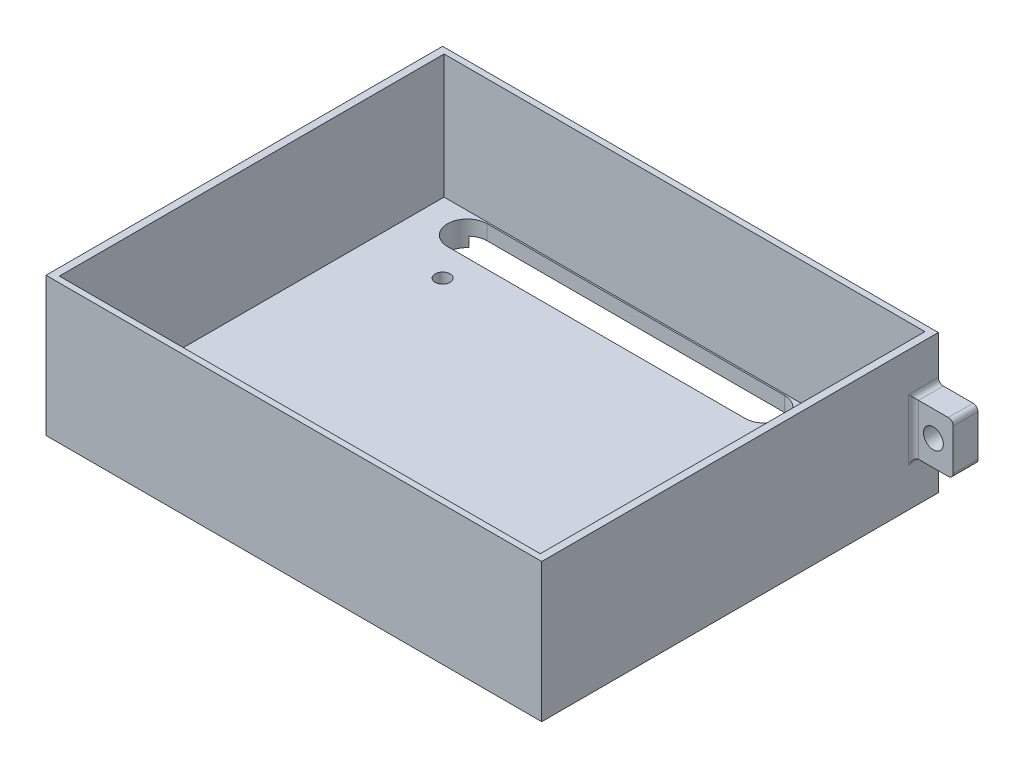
SolidWorks part; units mm, degrees
ref_plane "Front" through (0, 0, 0) normal (0, 0, 1) x (1, 0, 0)
ref_plane "Top" through (0, 0, 0) normal (0, 1, 0) x (1, 0, 0)
ref_plane "Right" through (0, 0, 0) normal (1, 0, 0) x (0, 0, -1)
sketch "Sketch1" plane through (0, 0, 0) normal (0, 1, 0) x (1, 0, 0)
  line L1 (-50, -40) -> (50, -40)
  line L2 (-50, -40) -> (-50, 40)
  line L3 (-50, 40) -> (50, 40)
  line L4 (50, -40) -> (50, 40)
  line L5 (-50, -40) -> (50, 40) construction
  line L6 (-50, 40) -> (50, -40) construction
  point P0 (0, 0)
  dimension "D1" = 100
  dimension "D2" = 80
extrude "Boss-Extrude1" add sketch "Sketch1" along normal blind 3
sketch "Sketch2" plane through (0, 3, 0) normal (0, 1, 0) x (1, 0, 0)
  line L1 (-50, -40) -> (50, -40)
  line L2 (-50, -40) -> (-50, 40)
  line L3 (-50, 40) -> (50, 40)
  line L4 (50, -40) -> (50, 40)
  line L5 (-50, -40) -> (50, 40) construction
  line L6 (-50, 40) -> (50, -40) construction
  line L7 (-48.5, -38.8) -> (48.5, -38.8)
  line L8 (-48.5, -38.8) -> (-48.5, 38.8)
  line L9 (-48.5, 38.8) -> (48.5, 38.8)
  line L10 (48.5, -38.8) -> (48.5, 38.8)
  line L11 (-48.5, -38.8) -> (48.5, 38.8) construction
  line L12 (-48.5, 38.8) -> (48.5, -38.8) construction
  point P0 (0, 0)
  point P7 (0, 0)
  dimension "D1" = 97
extrude "Boss-Extrude2" add sketch "Sketch2" along normal blind 25
sketch "Sketch3" plane through (0, 3, 0) normal (0, 1, 0) x (1, 0, 0)
  line L0 (-39.5, 34.5) -> (20.5, 34.5) construction
  line L1 (-39.5, 38.5) -> (20.5, 38.5)
  line L2 (-39.5, 30.5) -> (20.5, 30.5)
  line L3 (50, 40) -> (-50, 40) construction
  line L4 (-50, 40) -> (-50, -40) construction
  circle A0 centre (-34.5, 24.5) radius 1.5
  circle A1 centre (34.5, 24.5) radius 1.5
  circle A2 centre (-34.5, -24.5) radius 1.5
  circle A3 centre (34.5, -24.5) radius 1.5
  arc A4 (-39.5, 38.5) -> (-39.5, 30.5) centre (-39.5, 34.5) ccw
  arc A5 (20.5, 30.5) -> (20.5, 38.5) centre (20.5, 34.5) ccw
  point P2 (0, 0)
  point P15 (-9.5, 34.5)
  dimension "D5" = 60
  dimension "D3" = 3
  dimension "D4" = 4
  dimension "D6" = 2
  dimension "D1" = 15.5
  dimension "D2" = 15.5
  dimension "D8" = 25
  dimension "D7" = 2
  dimension "D9" = 10
extrude "Cut-Extrude1" cut sketch "Sketch3" against normal blind 40
sketch "Sketch4" plane through (0, 3, 0) normal (0, 1, 0) x (1, 0, 0)
  line L2 (47.5, -37.5) -> (-47.5, -37.5)
  line L3 (47.5, -37.5) -> (47.5, 37.5)
  line L4 (47.5, 37.5) -> (-47.5, 37.5)
  line L5 (-47.5, -37.5) -> (-47.5, 37.5)
  line L6 (47.5, -37.5) -> (-47.5, 37.5) construction
  line L8 (47.5, 37.5) -> (-47.5, -37.5) construction
  point P0 (0, 0)
  dimension "D1" = 95
  dimension "D2" = 75
extrude "Boss-Extrude3" add sketch "Sketch4" against normal blind 5
extrude "Cut-Extrude2" cut sketch "Sketch3<2>" against normal blind 12
sketch "Sketch3<2>" plane through (0, 3, 0) normal (0, 1, 0) x (1, 0, 0) same geometry as "Sketch3"
sketch "Sketch6" plane through (0, 0, -40) normal (0, 0, -1) x (-1, 0, 0)
  line L0 (-50, 28) -> (50, 28) construction
  line L1 (-58, 8.85) -> (-50, 8.85)
  line L2 (-58, 8.85) -> (-58, 19.15)
  line L3 (-58, 19.15) -> (-50, 19.15)
  line L4 (-50, 8.85) -> (-50, 19.15)
  line L5 (-58, 8.85) -> (-50, 19.15) construction
  line L6 (-58, 19.15) -> (-50, 8.85) construction
  line L7 (50, 8.85) -> (58, 8.85)
  line L8 (50, 8.85) -> (50, 19.15)
  line L9 (50, 19.15) -> (58, 19.15)
  line L10 (58, 8.85) -> (58, 19.15)
  line L11 (50, 8.85) -> (58, 19.15) construction
  line L12 (50, 19.15) -> (58, 8.85) construction
  circle A0 centre (-54, 14) radius 2
  circle A1 centre (54, 14) radius 2
  point P0 (-54, 14)
  point P9 (54, 14)
  dimension "D6" = 4
  dimension "D7" = 4
  dimension "D1" = 10.3
  dimension "D2" = 8
  dimension "D3" = 14
  dimension "D4" = 54
  dimension "D5" = 2
extrude "Boss-Extrude4" add sketch "Sketch6" against normal blind 5
fillet "Fillet1" radius 1 1 edges type face fillet first side face at (50, 15.1062, -18.125) second side face at (55, 8.85, -36.875)
fillet "Fillet2" radius 1 1 edges at (58, 8.85, -37.5) type face fillet first side face at (55.375, 8.85, -37.5) second side face at (58, 14, -37.5)
fillet "Fillet3" radius 1 1 edges at (58, 19.15, -37.5) type face fillet first side face at (58, 14.5, -37.5) second side face at (53, 19.15, -36.875)
fillet "Fillet4" radius 1 1 edges type face fillet first side face at (50, 14.7937, -18.4375) second side face at (52.625, 19.15, -36.875)
fillet "Fillet5" radius 1 1 edges at (50, 14, -35) type face fillet first side face at (52, 14, -35) second side face at (50, 14.9812, -18.75)
fillet "Fillet6" radius 1 1 edges at (-58, 8.85, -37.5) type face fillet first side face at (-58, 14, -37.5) second side face at (-53, 8.85, -36.875)
fillet "Fillet7" radius 1 1 edges at (-58, 19.15, -37.5) type face fillet first side face at (-55, 19.15, -36.875) second side face at (-58, 14.5, -37.5)
fillet "Fillet8" radius 1 1 edges type face fillet first side face at (-50, 15.1062, -18.125) second side face at (-54.375, 19.15, -36.875)
fillet "Fillet9" radius 1 1 edges type face fillet first side face at (-52.625, 8.85, -36.875) second side face at (-50, 15.2937, -18.4375)
fillet "Fillet10" radius 1 1 edges at (-50, 14, -35) type face fillet first side face at (-56, 14, -35) second side face at (-50, 14.9812, -18.75)
